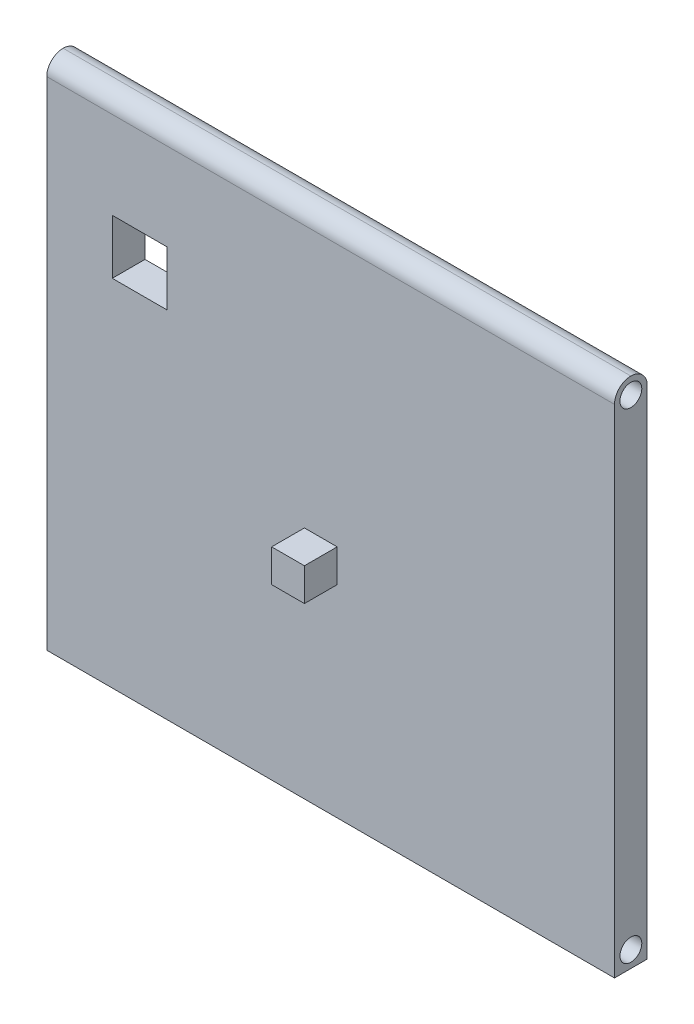
SolidWorks part; units mm, degrees
ref_plane "前视基准面" through (0, 0, 0) normal (0, 0, 1) x (1, 0, 0)
ref_plane "上视基准面" through (0, 0, 0) normal (0, 1, 0) x (1, 0, 0)
ref_plane "右视基准面" through (0, 0, 0) normal (1, 0, 0) x (0, 0, -1)
other "Configuration Table"
sketch "草图1" plane through (0, 0, 0) normal (0, 0, 1) x (1, 0, 0)
  line L1 (-16.4733, 7.2443) -> (35.5267, 7.2443)
  line L2 (-16.4733, 7.2443) -> (-16.4733, -39.7557)
  line L3 (-16.4733, -39.7557) -> (35.5267, -39.7557)
  line L4 (35.5267, 7.2443) -> (35.5267, -39.7557)
  dimension "D1" = 52
  dimension "D2" = 47
extrude "凸台-拉伸1" add sketch "草图1" along normal blind 3
ref_plane "基准面1" through (35.5267, 0, 0) normal (1, 0, 0) x (0, 0, -1)
sketch "草图2" plane through (35.5267, 0, 0) normal (1, 0, 0) x (0, 0, -1)
  line L0 (-3, 7.2443) -> (0, 7.2443) construction
  line L1 (0, -39.7557) -> (0, 7.2443) construction
  circle A0 centre (-1.5, 5.7443) radius 1
  dimension "D1" = 2
  dimension "D2" = 1.5
  dimension "D3" = 1.5
extrude "切除-拉伸1" cut sketch "草图2" against normal blind 92
fillet "圆角1" radius 1.5 1 edges at (9.5267, 7.2443, 0)
fillet "圆角2" radius 1.5 1 edges at (9.5267, 7.2443, 3)
sketch "草图3" plane through (35.5267, 0, 0) normal (1, 0, 0) x (0, 0, -1)
  line L0 (-3, -39.7557) -> (-3, 5.7443) construction
  line L1 (-3, -39.7557) -> (0, -39.7557) construction
  circle A0 centre (-1.5, -38.2557) radius 1
  point P6 (-0.9168, -39.7557)
  dimension "D1" = 2
  dimension "D2" = 1.5
  dimension "D3" = 1.5
extrude "切除-拉伸2" cut sketch "草图3" against normal blind 92
ref_plane "基准面2" through (0, 0, 3) normal (0, 0, 1) x (1, 0, 0)
sketch "草图4" plane through (0, 0, 3) normal (0, 0, 1) x (1, 0, 0)
  line L0 (-16.4733, -39.7557) -> (35.5267, -39.7557) construction
  line L1 (7.1267, -18.2557) -> (10.1267, -18.2557)
  line L2 (7.1267, -18.2557) -> (7.1267, -21.2557)
  line L3 (7.1267, -21.2557) -> (10.1267, -21.2557)
  line L4 (10.1267, -18.2557) -> (10.1267, -21.2557)
  line L5 (35.5267, -39.7557) -> (35.5267, 5.7443) construction
  point P4 (8.6267, -21.2557)
  dimension "D1" = 3
  dimension "D2" = 3
  dimension "D3" = 18.5
  dimension "D4" = 25.4
extrude "凸台-拉伸2" add sketch "草图4" along normal blind 3
ref_plane "基准面3" through (0, 0, 0) normal (0, 0, -1) x (-1, 0, 0)
sketch "草图5" plane through (0, 0, 0) normal (0, 0, -1) x (-1, 0, 0)
  line L0 (16.4733, 5.7443) -> (-35.5267, 5.7443) construction
  line L1 (5.4733, -2.2557) -> (10.4733, -2.2557)
  line L2 (5.4733, -2.2557) -> (5.4733, -7.2557)
  line L3 (5.4733, -7.2557) -> (10.4733, -7.2557)
  line L4 (10.4733, -2.2557) -> (10.4733, -7.2557)
  line L5 (16.4733, 5.7443) -> (16.4733, -39.7557) construction
  point P4 (7.9733, -2.2557)
  dimension "D1" = 5
  dimension "D2" = 5
  dimension "D3" = 8
  dimension "D4" = 6
extrude "切除-拉伸3" cut sketch "草图5" against normal blind 6
